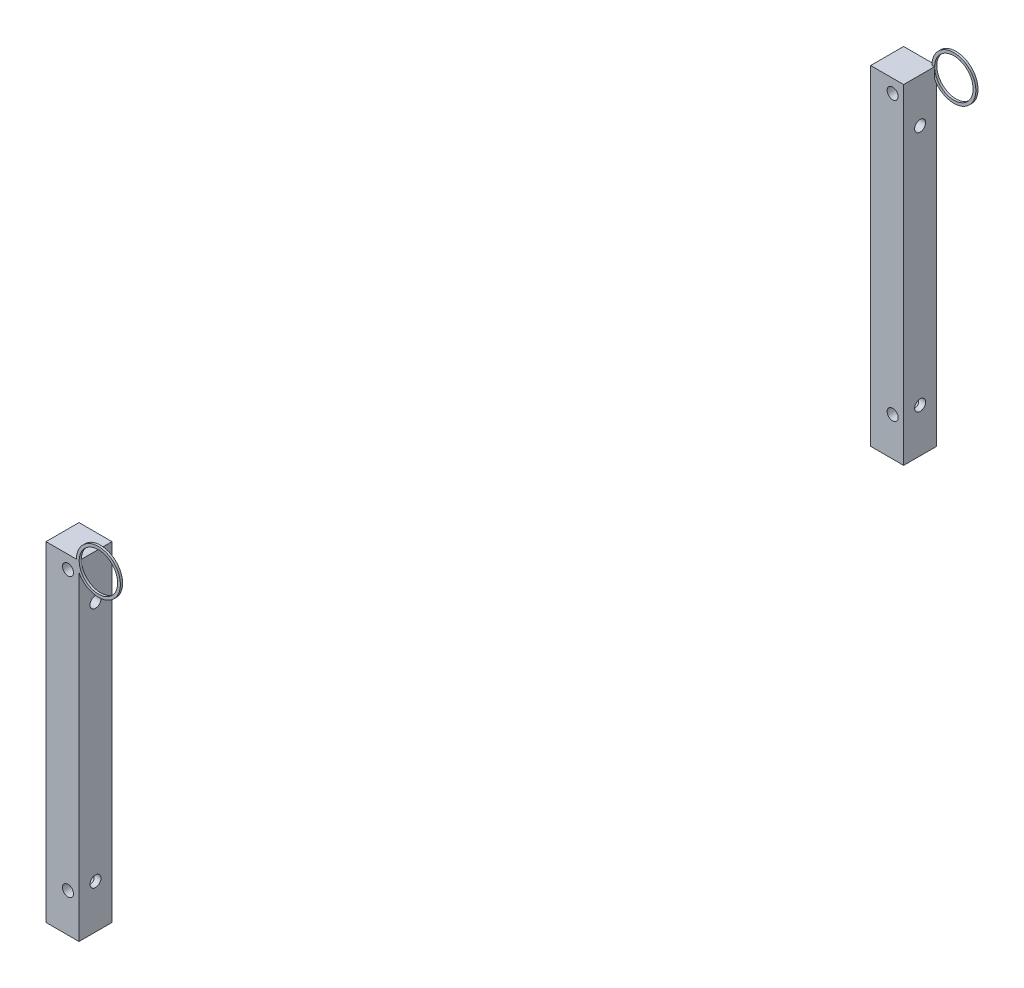
SolidWorks part; units mm, degrees
ref_plane "Front Plane" through (0, 0, 0) normal (0, 0, 1) x (1, 0, 0)
ref_plane "Top Plane" through (0, 0, 0) normal (0, 1, 0) x (1, 0, 0)
ref_plane "Right Plane" through (0, 0, 0) normal (1, 0, 0) x (0, 0, -1)
sketch "Sketch1" plane through (0, 0, 0) normal (0, 1, 0) x (1, 0, 0)
  line L1 (-15, 15) -> (15, 15)
  line L2 (-15, 15) -> (-15, -15)
  line L3 (-15, -15) -> (15, -15)
  line L4 (15, 15) -> (15, -15)
  line L5 (-15, 15) -> (15, -15) construction
  line L6 (-15, -15) -> (15, 15) construction
  point P0 (0, 0)
  dimension "D1" = 30
  dimension "D2" = 30
extrude "Boss-Extrude1" add sketch "Sketch1" along normal blind 300
sketch "Sketch2" plane through (0, 0, 15) normal (0, 0, 1) x (1, 0, 0)
  line L1 (15, 300) -> (35, 300) construction
  circle A0 centre (32.6669, 300) radius 20
  dimension "D1" = 40
extrude "Boss-Extrude2" add sketch "Sketch2" against normal blind 2
sketch "Sketch3" plane through (0, 0, 15) normal (0, 0, 1) x (1, 0, 0)
  circle A0 centre (32.6669, 300) radius 17.5
  dimension "D1" = 35
extrude "Cut-Extrude1" cut sketch "Sketch3" against normal blind 30
ref_plane "Plane1" through (0, 0, -375) normal (0, 0, -1) x (-1, 0, 0)
sketch "Sketch4" plane through (15, 0, 0) normal (1, 0, 0) x (0, 0, -1)
  line L0 (0, 260) -> (0, 300) construction
  line L1 (-13, 300) -> (15, 300) construction
  line L2 (0, 265) -> (0, 260) construction
  line L3 (0, 0) -> (0, 40) construction
  circle A0 centre (0, 260) radius 5
  circle A1 centre (0, 40) radius 5
  dimension "D2" = 10
  dimension "D4" = 10
  dimension "D1" = 40
  dimension "D3" = 40
extrude "Cut-Extrude2" cut sketch "Sketch4" against normal through all
sketch "Sketch5" plane through (0, 0, 15) normal (0, 0, 1) x (1, 0, 0)
  line L0 (-15, 300) -> (12.6669, 300) construction
  line L1 (5, 287.9907) -> (-15, 287.9907) construction
  line L2 (-15, 300) -> (-15, 0) construction
  line L3 (5, 35.0718) -> (-15, 35.0718) construction
  circle A0 centre (5, 287.9907) radius 5
  circle A1 centre (5, 35.0718) radius 5
  point P0 (5, 287.9907)
  point P1 (5, 35.0718)
  point P4 (-1.1665, 300)
  dimension "D3" = 10
  dimension "D4" = 10
  dimension "D1" = 13.5
  dimension "D2" = 265
  dimension "D5" = 20
  dimension "D6" = 20
extrude "Cut-Extrude3" cut sketch "Sketch5" against normal through all
shell "Shell1" thickness 1 removed face at (0, 0, 0)
mirror "Mirror1" about plane through (0, 0, -375) normal (0, 0, -1) of bodies 112
